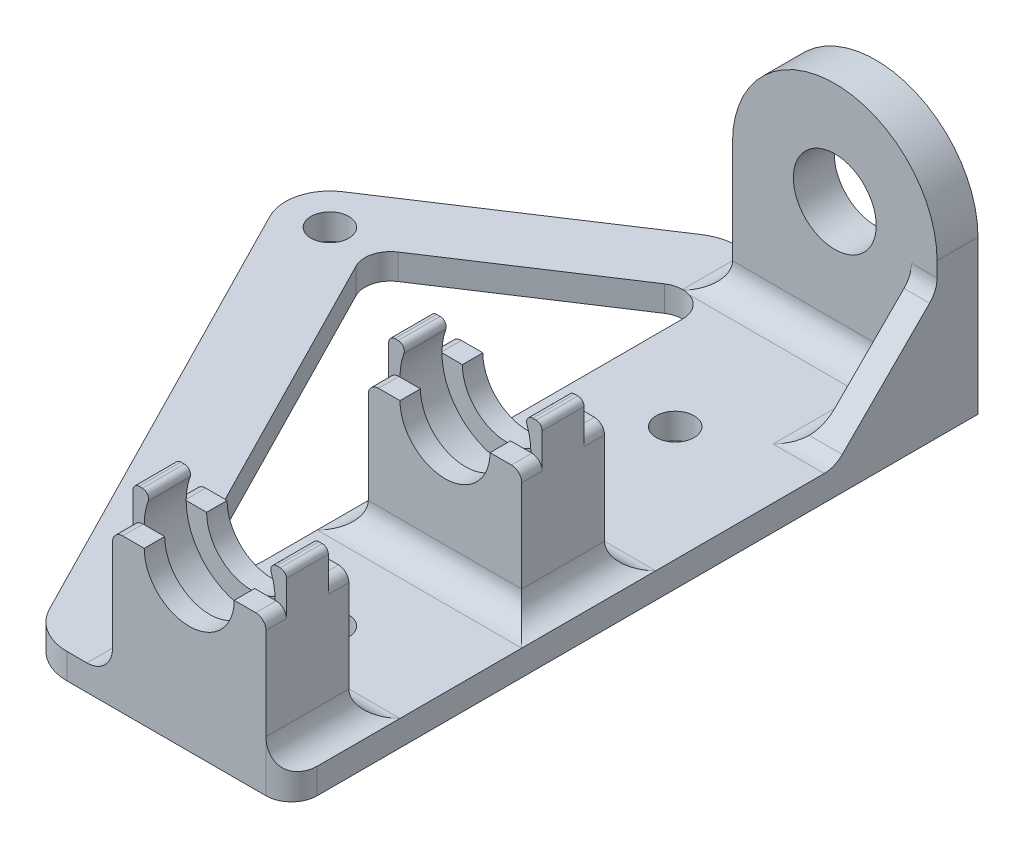
SolidWorks part; units mm, degrees
ref_plane "Front Plane" through (0, 0, 0) normal (0, 0, 1) x (1, 0, 0)
ref_plane "Top Plane" through (0, 0, 0) normal (0, 1, 0) x (1, 0, 0)
ref_plane "Right Plane" through (0, 0, 0) normal (1, 0, 0) x (0, 0, -1)
sketch "Sketch1" plane through (0, 0, 0) normal (0, 0, 1) x (1, 0, 0)
  line L0 (-8.763, 22.86) -> (-8.3512, 22.86)
  line L1 (-9.525, 0) -> (9.525, 0)
  line L2 (-9.525, 0) -> (-9.525, 22.098)
  line L3 (8.3512, 22.86) -> (8.763, 22.86)
  line L4 (9.525, 0) -> (9.525, 22.098)
  line L5 (0, 19.05) -> (0, 0) construction
  arc A0 (-7.6353, 21.8367) -> (7.6353, 21.8367) centre (0, 19.05) ccw
  arc A1 (8.763, 22.86) -> (9.525, 22.098) centre (8.763, 22.098) cw
  arc A2 (-9.525, 22.098) -> (-8.763, 22.86) centre (-8.763, 22.098) cw
  arc A3 (7.6353, 21.8367) -> (8.3512, 22.86) centre (8.3512, 22.098) cw
  arc A4 (-7.6353, 21.8367) -> (-8.3512, 22.86) centre (-8.3512, 22.098) ccw
  point P4 (0, 0)
  point P15 (7.1797, 22.86)
  dimension "D2" = 16.256
  dimension "D5" = 0.762
  dimension "D6" = 0.762
  dimension "D1" = 19.05
  dimension "D3" = 19.05
  dimension "D4" = 3.81
extrude "Boss-Extrude1" add sketch "Sketch1" along normal mid plane 5.207
sketch "Sketch2" plane through (0, 0, 2.6035) normal (0, 0, 1) x (1, 0, 0)
  line L0 (9.525, 0) -> (9.525, 22.098) construction
  line L1 (-9.525, 0) -> (9.525, 0)
  line L2 (-9.525, 0) -> (-9.525, 19.05)
  line L3 (-9.525, 19.05) -> (-5.588, 19.05)
  line L4 (9.525, 0) -> (9.525, 19.05)
  line L5 (5.588, 19.05) -> (9.525, 19.05)
  arc A0 (-5.588, 19.05) -> (5.588, 19.05) centre (0, 19.05) ccw
  arc A1 (-7.6353, 21.8367) -> (7.6353, 21.8367) centre (0, 19.05) ccw construction
  dimension "D2" = 2.54
  dimension "D1" = 19.05
extrude "Boss-Extrude2" add sketch "Sketch2" along normal blind 2.54
fillet "Fillet1" radius 1.27 2 edges
mirror "Mirror1" about plane through (0, 0, 0) normal (0, 0, 1) of "Fillet1", "Boss-Extrude2"
pattern_linear "LPattern1" count 2 spacing 31.75 along (0, 0, -1) of "Boss-Extrude1", "Boss-Extrude2", "Mirror1"
sketch "Sketch3" plane through (0, 0, 0) normal (0, 1, 0) x (1, 0, 0)
  line L0 (0, 80.0735) -> (0, 0) construction
  line L1 (-12.7, 80.0735) -> (12.7, 80.0735)
  line L2 (-12.7, 80.0735) -> (-12.7, 74.9935)
  line L3 (-12.7, 74.9935) -> (12.7, 74.9935)
  line L4 (12.7, 80.0735) -> (12.7, 74.9935)
  line L5 (5.588, 36.8935) -> (-5.588, 36.8935) construction
  dimension "D1" = 5.08
  dimension "D2" = 25.4
  dimension "D3" = 38.1
extrude "Boss-Extrude3" add sketch "Sketch3" along normal blind 38.1 separate body
sketch "Sketch5" plane through (0, 0, -74.9935) normal (0, 0, 1) x (1, 0, 0)
  line L0 (0, 19.05) -> (0, 0) construction
  line L1 (-12.7, 38.1) -> (-12.7, 0) construction
  line L2 (12.7, 38.1) -> (12.7, 0) construction
  line L3 (-12.7, 19.05) -> (-12.7, 38.1)
  line L4 (-12.7, 38.1) -> (12.7, 38.1)
  line L5 (12.7, 38.1) -> (12.7, 19.05)
  circle A0 centre (0, 19.05) radius 5.1435
  arc A1 (-5.588, 19.05) -> (5.588, 19.05) centre (0, 19.05) ccw construction
  arc A2 (-12.7, 19.05) -> (12.7, 19.05) centre (0, 19.05) cw
  dimension "D1" = 10.287
extrude "Cut-Extrude1" cut sketch "Sketch5" against normal through all
sketch "Sketch7" plane through (0, 0, 0) normal (0, 1, 0) x (1, 0, 0)
  line L0 (-9.525, -5.1435) -> (9.525, -5.1435) construction
  line L1 (9.525, -5.1435) -> (-15.1619, -5.1435)
  line L2 (12.7, -1.9685) -> (12.7, 80.0735)
  line L3 (12.7, 80.0735) -> (-17.1501, 80.0735)
  line L4 (-37.5809, 58.3316) -> (-17.6188, 71.4513)
  line L5 (12.7, 80.0735) -> (-12.7, 80.0735) construction
  line L6 (-1.5875, 56.769) -> (-44.45, 56.769) construction
  line L7 (-1.5875, 56.769) -> (-1.5875, 13.9065) construction
  line L8 (-1.5875, 13.9065) -> (-28.7739, 13.9065) construction
  line L9 (-44.45, 56.769) -> (-44.45, 44.6175) construction
  line L10 (12.7, 74.9935) -> (12.7, 80.0735) construction
  line L11 (-20.6377, 79.03) -> (-47.4842, 61.3857)
  line L12 (-49.3705, 54.2574) -> (-20.8177, -1.6804)
  line L13 (-19.05, 80.0735) -> (-19.05, -5.1435) construction
  line L14 (-12.7, 80.0735) -> (-12.7, 74.9935) construction
  line L15 (-12.7, 68.7981) -> (-12.7, 16.5708)
  line L16 (-9.525, 26.6065) -> (-9.525, 36.8935) construction
  line L17 (-38.665, 54.2349) -> (-18.7029, 15.1273)
  circle A0 centre (-1.5875, 13.9065) radius 2.3495
  circle A1 centre (-1.5875, 56.769) radius 2.3495
  circle A2 centre (-44.45, 56.769) radius 2.3495
  arc A3 (-20.8177, -1.6804) -> (-15.1619, -5.1435) centre (-15.1619, 1.2065) ccw
  arc A4 (-49.3705, 54.2574) -> (-47.4842, 61.3857) centre (-44.45, 56.769) cw
  arc A5 (-20.6377, 79.03) -> (-17.1501, 80.0735) centre (-17.1501, 73.7235) cw
  arc A6 (9.525, -5.1435) -> (12.7, -1.9685) centre (9.525, -1.9685) ccw
  arc A7 (-12.7, 16.5708) -> (-18.7029, 15.1273) centre (-15.875, 16.5708) cw
  arc A8 (-37.5809, 58.3316) -> (-38.665, 54.2349) centre (-35.8371, 55.6784) ccw
  arc A9 (-17.6188, 71.4513) -> (-12.7, 68.7981) centre (-15.875, 68.7981) cw
  point P38 (-39.9585, 56.769)
  dimension "D1" = 4.699
  dimension "D2" = 19.05
  dimension "D5" = 42.8625
  dimension "D6" = 6.35
  dimension "D7" = 3.175
  dimension "D8" = 6.35
  dimension "D9" = 3.175
  dimension "D10" = 3.175
  dimension "D3" = 42.8625
  dimension "D4" = 1.5875
  dimension "D11" = 9.525
  dimension "D12" = 3.175
extrude "Boss-Extrude4" add sketch "Sketch7" along normal blind 3.175
sketch "Sketch8" plane through (12.7, 0, 0) normal (1, 0, 0) x (0, 0, -1)
  line L0 (62.2935, 3.175) -> (74.9935, 15.875)
  line L1 (-1.9685, 3.175) -> (74.9935, 3.175) construction
  line L2 (74.9935, 19.05) -> (74.9935, 3.175) construction
  line L3 (74.9935, 15.875) -> (74.9935, 3.175)
  line L4 (74.9935, 3.175) -> (62.2935, 3.175)
  dimension "D1" = 12.7
extrude "Boss-Extrude5" add sketch "Sketch8" against normal blind 3.175
fillet "Fillet2" radius 3.175 12 edges at (11.1125, 3.175, -62.2935) (11.1125, 15.875, -74.9935) (0, 3.175, -5.1435) (0, 3.175, -36.8935) (0, 3.175, -26.6065) (-12.7, 3.175, -77.5335) (9.525, 3.175, -68.6435) (-1.5875, 3.175, -74.9935) (-9.525, 3.175, 0) (-9.525, 3.175, -31.75) (9.525, 3.175, 0) (9.525, 3.175, -31.75)
